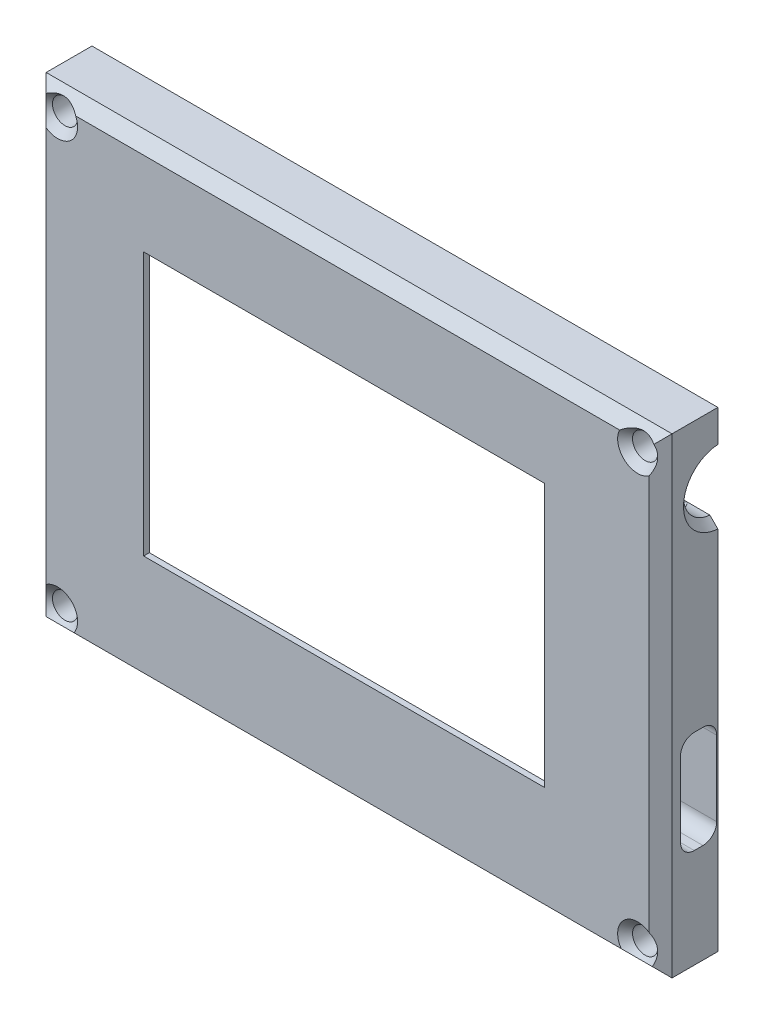
SolidWorks part; units mm, degrees
ref_plane "Front Plane" through (0, 0, 0) normal (0, 0, 1) x (1, 0, 0)
ref_plane "Top Plane" through (0, 0, 0) normal (0, 1, 0) x (1, 0, 0)
ref_plane "Right Plane" through (0, 0, 0) normal (1, 0, 0) x (0, 0, -1)
sketch "Sketch1" plane through (0, 0, 0) normal (0, 0, 1) x (1, 0, 0)
  line L1 (0, 41.15) -> (54.65, 41.15)
  line L2 (0, 41.15) -> (0, 0)
  line L3 (0, 0) -> (54.65, 0)
  line L4 (54.65, 41.15) -> (54.65, 0)
  point P6 (2, 39.4)
  point P7 (52.65, 2)
  dimension "D1" = 54.65
  dimension "D2" = 41.15
  dimension "D3" = 1.75
  dimension "D4" = 2
  dimension "D5" = 2
  dimension "D6" = 2
extrude "Boss-Extrude1" add sketch "Sketch1" along normal blind 5
sketch "Sketch2" plane through (0, 0, 5) normal (0, 0, 1) x (1, 0, 0)
  line L0 (0, 41.15) -> (0, 0) construction
  line L1 (9.51, 32.84) -> (44.51, 32.84)
  line L2 (9.51, 32.84) -> (9.51, 9.84)
  line L3 (9.51, 9.84) -> (44.51, 9.84)
  line L4 (44.51, 32.84) -> (44.51, 9.84)
  line L5 (0, 0) -> (54.65, 0) construction
  line L6 (54.65, 0) -> (54.65, 41.15) construction
  line L7 (54.65, 41.15) -> (0, 41.15) construction
  dimension "D1" = 9.51
  dimension "D2" = 9.84
  dimension "D3" = 10.14
  dimension "D4" = 8.31
extrude "Cut-Extrude1" cut sketch "Sketch2" against normal blind 1.5
sketch "Sketch3" plane through (0, 0, 0) normal (0, 0, -1) x (-1, 0, 0)
  line L1 (-51.15, 37.65) -> (-3.5, 37.65)
  line L2 (-51.15, 37.65) -> (-51.15, 3.5)
  line L3 (-51.15, 3.5) -> (-3.5, 3.5)
  line L4 (-3.5, 37.65) -> (-3.5, 3.5)
  line L7 (-54.65, 0) -> (-54.65, 41.15) construction
  line L8 (0, 0) -> (-54.65, 0) construction
  line L9 (-54.65, 41.15) -> (0, 41.15) construction
  line L10 (0, 41.15) -> (0, 0) construction
  dimension "D1" = 3.5
  dimension "D2" = 3.5
  dimension "D3" = 3.5
  dimension "D4" = 3.5
extrude "Cut-Extrude2" cut sketch "Sketch3" against normal offset from surface (4.5 mm away) 1 up to face at (27.01, 21.34, 3.5) offset beyond the face yes
sketch "Sketch4" plane through (54.65, 0, 0) normal (1, 0, 0) x (0, 0, -1)
  line L0 (-5, 41.15) -> (0, 41.15) construction
  line L2 (-2.3, 35.15) -> (-2.3, 33.3097) construction
  line L3 (0, 35.15) -> (0, 32.3033) construction
  line L4 (0, 0) -> (0, 41.15) construction
  circle A0 centre (0.2, 35.15) radius 2.5
  dimension "D1" = 5
  dimension "D3" = 2.3
  dimension "D2" = 6
extrude "Cut-Extrude3" cut sketch "Sketch4" against normal blind 4
chamfer "Chamfer1" distance 0.7 angle 45 1 edges at (54.65, 35.15, 2.3)
sketch "Sketch5" plane through (0, 0, 5) normal (0, 0, 1) x (1, 0, 0)
  line L0 (0, 0) -> (54.65, 0) construction
  line L1 (54.65, 0) -> (54.65, 41.15) construction
  line L2 (54.65, 41.15) -> (0, 41.15) construction
  line L3 (0, 41.15) -> (0, 0) construction
  line L4 (0, 20.575) -> (54.65, 20.575) construction
  line L6 (27.325, 41.15) -> (27.325, 0) construction
  point P0 (52.65, 2)
  point P1 (2, 39.4)
  point P19 (52.65, 39.4)
  point P20 (2, 2)
  dimension "D1" = 2
  dimension "D2" = 2
  dimension "D3" = 1.75
  dimension "D4" = 2
hole_wizard "CSK for M3 Flat Head Machine Screw1" positions "Sketch5" profile "Sketch6" countersink size "M3" standard "ANSI Metric"
sketch "Sketch6" plane through (52.65, 2, 5) normal (1, 0, 0) x (0, -1, 0)
  line L0 (0, 0) -> (0, 6.6609)
  line L1 (0, 6.6609) -> (1.1, 6)
  line L2 (1.1, 6) -> (1.1, 0.65)
  line L3 (1.1, 0.65) -> (1.75, 0)
  line L5 (1.75, 0) -> (0, 0)
  line L6 (-1.1, 0.65) -> (-1.75, 0) construction
  line L10 (0, 6.6609) -> (-1.1, 6) construction
  line L11 (0, -6.35) -> (0, 107.95) construction
  dimension "Hole Dia." = 2.2
  dimension "Hole Depth" = 6
  dimension "Near C'Sink Dia." = 3.5
  dimension "Near C'Sink Angle" = 90
  dimension "Drill Angle" = 118
chamfer "Chamfer2" distance 1 angle 45 4 edges at (27.325, 41.15, 5) (54.65, 20.575, 5) (27.325, 0, 5) (0, 20.575, 5)
fillet "Fillet3" radius 0.75 1 edges at (51.15, 35.15, 2.3)
sketch "Sketch7" plane through (54.65, 0, 0) normal (1, 0, 0) x (0, 0, -1)
  line L0 (0, 8.67) -> (0, 17.61)
  line L1 (0, 8.67) -> (-3.26, 8.67)
  line L2 (-3.26, 8.67) -> (-3.26, 17.61)
  line L3 (0, 17.61) -> (-3.26, 17.61)
  line L4 (-4.5, 3.5) -> (0, 3.5) construction
  line L5 (-4.5, 3.5) -> (0, 3.5) construction
  line L6 (0, 0) -> (0, 31.9563) construction
  line L7 (-4, 41.15) -> (-4, 0) construction
  line L8 (-4, 41.15) -> (0, 41.15) construction
  dimension "D1" = 8.94
  dimension "D2" = 3.26
  dimension "D3" = 5.17
extrude "Cut-Extrude4" cut sketch "Sketch7" against normal up to next
fillet "Fillet4" radius 1.2 2 edges at (52.9, 8.67, 3.26) (52.9, 17.61, 3.26)
sketch "Sketch8" plane through (0, 0, 0) normal (0, 0, -1) x (-1, 0, 0)
  line L1 (-54.65, 17.61) -> (-51.15, 17.61)
  line L2 (-54.65, 17.61) -> (-54.65, 8.67)
  line L3 (-54.65, 8.67) -> (-51.15, 8.67)
  line L4 (-51.15, 17.61) -> (-51.15, 8.67)
extrude "Boss-Extrude2" add sketch "Sketch8" along normal blind 10 and the other way blind 0.1
fillet "Fillet5" radius 1.2 2 edges at (52.9, 17.61, 0.1) (52.9, 8.67, 0.1)
sketch "Sketch9" plane through (0, 8.67, 0) normal (0, -1, 0) x (1, 0, 0)
  line L4 (54.65, 0) -> (51.15, 0)
  line L5 (51.15, 0) -> (51.15, -10)
  line L6 (51.15, -10) -> (54.65, -10)
  line L7 (54.65, -10) -> (54.65, 0)
  line L8 (54.65, 0) -> (51.15, 0)
  line L9 (51.15, 0) -> (51.15, -10)
  line L10 (51.15, -10) -> (54.65, -10)
  line L11 (54.65, -10) -> (54.65, 0)
  dimension "D1" = 0
extrude "Cut-Extrude5" cut sketch "Sketch9" against normal through all both and the other way through all
sketch "Sketch10" plane through (3.5, 0, 0) normal (1, 0, 0) x (0, 0, -1)
  line L4 (-4.5, 3.5) -> (0, 3.5)
  line L5 (0, 3.5) -> (0, 37.65)
  line L6 (0, 37.65) -> (-4.5, 37.65)
  line L7 (-4.5, 37.65) -> (-4.5, 3.5)
  line L8 (-4.5, 3.5) -> (0, 3.5)
  line L9 (0, 3.5) -> (0, 37.65)
  line L10 (0, 37.65) -> (-4.5, 37.65)
  line L11 (-4.5, 37.65) -> (-4.5, 3.5)
  dimension "D1" = 0
extrude "Cut-Extrude6" cut sketch "Sketch10" against normal offset from surface (2.3 mm away) 1.2 up to face at (0, 20.575, 2)
sketch "Sketch11" plane through (0, 0, 0) normal (0, 0, -1) x (-1, 0, 0)
  line L0 (-53.95, 37.642) -> (-51.9, 37.642) construction
  line L1 (-52.925, 37.642) -> (-49.8606, 37.642)
  line L2 (-52.925, 37.642) -> (-52.925, 32.658)
  line L3 (-52.925, 32.658) -> (-49.8606, 32.658)
  line L4 (-49.8606, 37.642) -> (-49.8606, 32.658)
extrude "Cut-Extrude7" cut sketch "Sketch11" against normal up to surface (4.5 mm away) up to face at (26.175, 20.575, 4.5)
fillet "Fillet6" radius 1 3 edges at (52.925, 37.642, 2.25) (52.925, 32.658, 2.25) (52.925, 35.15, 4.5)
